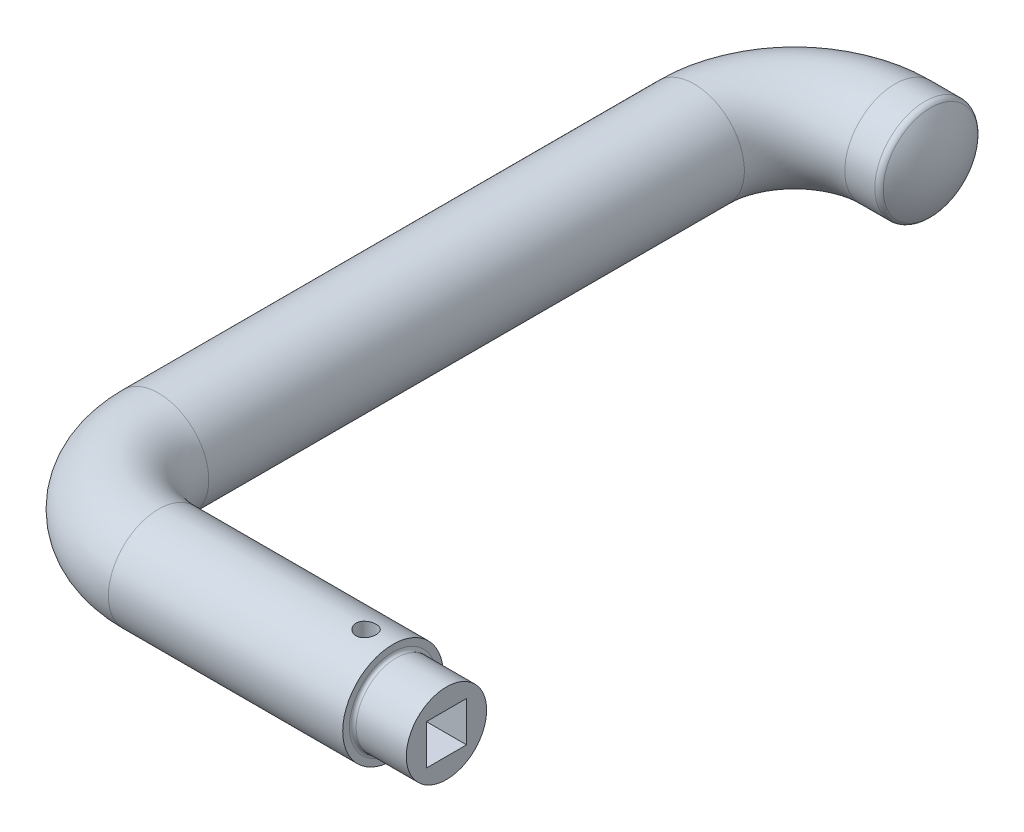
SolidWorks part; units mm, degrees
ref_plane "Front Plane" through (0, 0, 0) normal (0, 0, 1) x (1, 0, 0)
ref_plane "Top Plane" through (0, 0, 0) normal (0, 1, 0) x (1, 0, 0)
ref_plane "Right Plane" through (0, 0, 0) normal (1, 0, 0) x (0, 0, -1)
sketch "Sketch1" plane through (0, 0, 0) normal (0, 1, 0) x (1, 0, 0)
  line L0 (0, 0) -> (-27, 0)
  line L1 (-42, 15) -> (-42, 95)
  line L2 (-27, 110) -> (-22, 110)
  arc A0 (-27, 0) -> (-42, 15) centre (-27, 15) cw
  arc A1 (-42, 95) -> (-27, 110) centre (-27, 95) cw
  point P7 (-42, 0)
  point P10 (-42, 110)
  dimension "D1" = 42
  dimension "D2" = 110
  dimension "D4" = 15
  dimension "D3" = 20
sweep "Sweep-Thin1" add path "Sketch1" circular profile diameter 15 parameters "D1"=1.5, "D3"=15
sketch "Sketch63" plane through (0, 0, 0) normal (0, 1, 0) x (1, 0, 0)
  line L0 (-22, 110) -> (-19.5, 110)
  line L1 (-22, 102.5) -> (-22, 117.5) construction
  line L2 (-22, 117.5) -> (-22, 110)
  arc A0 (-22, 117.5) -> (-19.5, 110) centre (-32, 110) cw
  point P6 (-16.1889, 110)
  point P8 (0, 0)
  point P10 (0, 0)
  point P11 (0, 0)
  dimension "D1" = 12.5
  dimension "D2" = 2.5
revolve "Revolve1" add sketch "Sketch63" angle 360 about L0
sketch "Sketch64" plane through (0, 0, 0) normal (0, 1, 0) x (1, 0, 0)
  line L0 (0, 3) -> (0, 7.5)
  line L1 (0, -7.5) -> (0, 7.5) construction
  line L2 (0, 7.5) -> (8, 7.5)
  line L3 (8, 7.5) -> (8, 6)
  line L4 (8, 6) -> (16, 6)
  line L5 (16, 6) -> (16, 3)
  line L6 (16, 3) -> (0, 3)
  line L7 (0, 0) -> (23.5682, 0) construction
  dimension "D1" = 8
  dimension "D2" = 6
  dimension "D3" = 3
  dimension "D4" = 16
revolve "Revolve3" add sketch "Sketch64" angle 360 about L7
sketch "Sketch65" plane through (16, 0, 0) normal (1, 0, 0) x (0, 0, -1)
  line L1 (3, 3) -> (-3, 3)
  line L2 (3, 3) -> (3, -3)
  line L3 (3, -3) -> (-3, -3)
  line L4 (-3, 3) -> (-3, -3)
  line L5 (3, 3) -> (-3, -3) construction
  line L6 (3, -3) -> (-3, 3) construction
  point P0 (0, 0)
  point P6 (0, 0)
  point P7 (3, -3)
  dimension "D1" = 6
  dimension "D2" = 6
extrude "Cut-Extrude1" cut sketch "Sketch65" against normal up to surface (16 mm away) and the other way through all up to face at (0, 0, 3)
fillet "Fillet1" radius 0.5 1 edges at (8, 0, 6)
sketch "Sketch66" plane through (0, 0, 0) normal (0, 1, 0) x (1, 0, 0)
  line L0 (8, -7.5) -> (8, 7.5) construction
  circle A0 centre (4, 0) radius 1.5
  point P4 (0, 0)
  dimension "D1" = 3
  dimension "D2" = 4
extrude "Cut-Extrude2" cut sketch "Sketch66" along normal through all
fillet "Fillet2" radius 1 1 edges at (-22, 0, -102.5)
